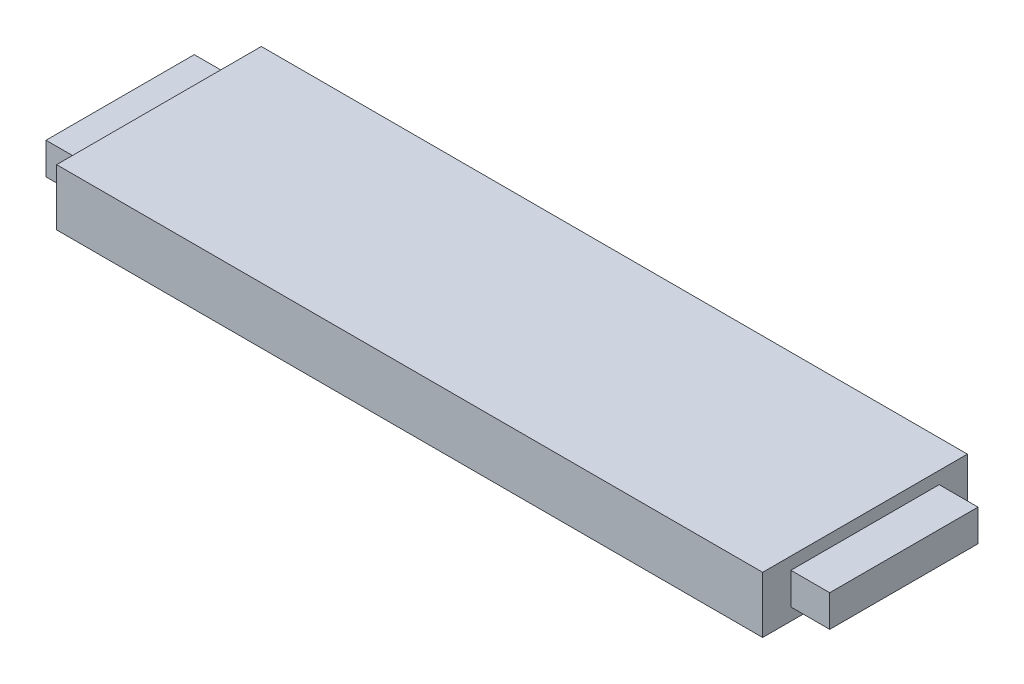
SolidWorks part; units mm, degrees
ref_plane "Спереди" through (0, 0, 0) normal (0, 0, 1) x (1, 0, 0)
ref_plane "Сверху" through (0, 0, 0) normal (0, 1, 0) x (1, 0, 0)
ref_plane "Справа" through (0, 0, 0) normal (1, 0, 0) x (0, 0, -1)
sketch "Эскиз1" plane through (0, 0, 0) normal (0, 1, 0) x (1, 0, 0)
  line L1 (-50, -14.4985) -> (50, -14.4985)
  line L2 (-50, -14.4985) -> (-50, 14.4985)
  line L3 (-50, 14.4985) -> (50, 14.4985)
  line L4 (50, -14.4985) -> (50, 14.4985)
  line L5 (-50, -14.4985) -> (50, 14.4985) construction
  line L6 (-50, 14.4985) -> (50, -14.4985) construction
  point P0 (0, 0)
  dimension "D1" = 28.997
  dimension "D2" = 100
extrude "Бобышка-Вытянуть1" add sketch "Эскиз1" along normal blind 8
sketch "Эскиз2" plane through (50, 0, 0) normal (1, 0, 0) x (0, 0, -1)
  line L0 (14.4985, 8) -> (-14.4985, 0) construction
  line L2 (-10.5009, 6.2506) -> (10.5009, 6.2506)
  line L3 (-10.5009, 6.2506) -> (-10.5009, 1.7494)
  line L4 (-10.5009, 1.7494) -> (10.5009, 1.7494)
  line L5 (10.5009, 6.2506) -> (10.5009, 1.7494)
  line L6 (-10.5009, 6.2506) -> (10.5009, 1.7494) construction
  line L7 (-10.5009, 1.7494) -> (10.5009, 6.2506) construction
  point P4 (0, 4)
extrude "Бобышка-Вытянуть2" add sketch "Эскиз2" along normal blind 5.5
sketch "Эскиз3" plane through (-50, 0, 0) normal (-1, 0, 0) x (0, 0, 1)
  line L0 (-14.4985, 0) -> (14.4985, 8) construction
  line L2 (10.4992, 1.752) -> (-10.4992, 1.752)
  line L3 (10.4992, 1.752) -> (10.4992, 6.248)
  line L4 (10.4992, 6.248) -> (-10.4992, 6.248)
  line L5 (-10.4992, 1.752) -> (-10.4992, 6.248)
  line L6 (10.4992, 1.752) -> (-10.4992, 6.248) construction
  line L7 (10.4992, 6.248) -> (-10.4992, 1.752) construction
  point P4 (0, 4)
extrude "Бобышка-Вытянуть3" add sketch "Эскиз3" along normal blind 5.5
